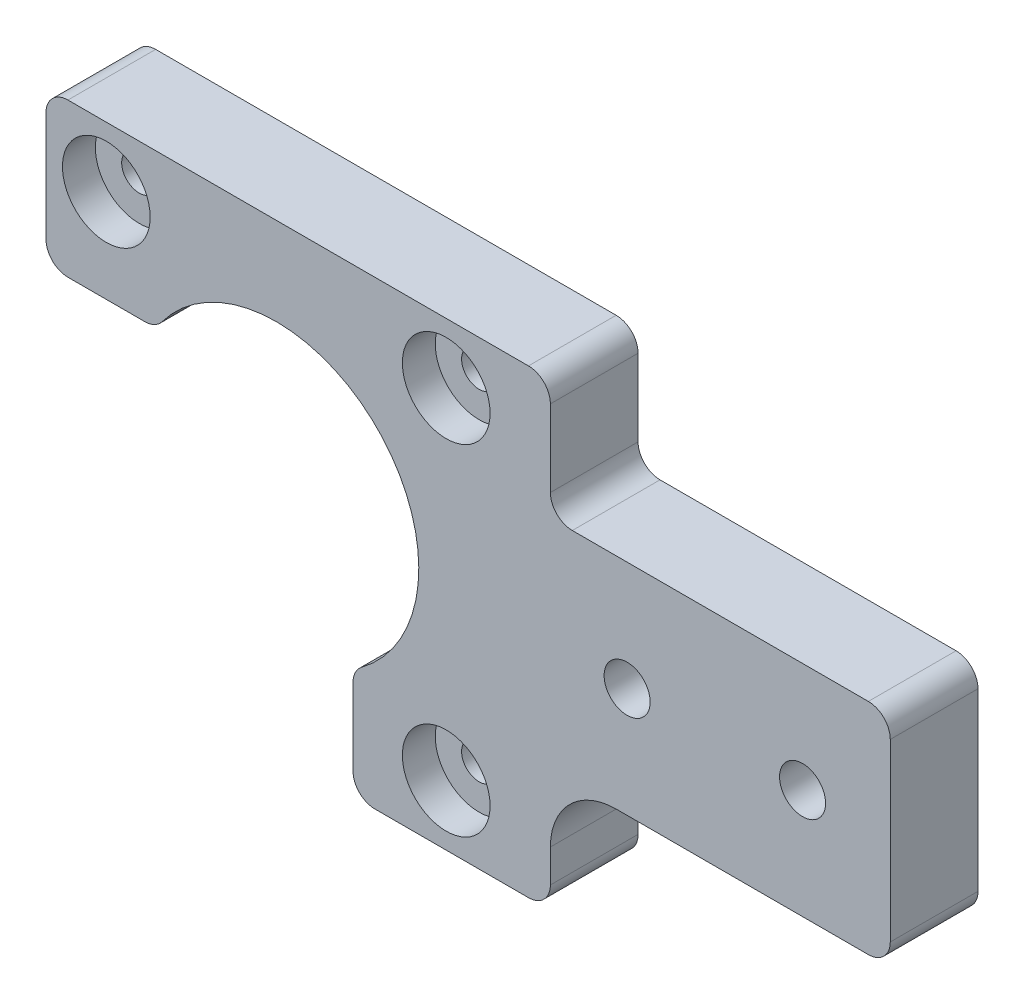
SolidWorks part; units mm, degrees
ref_plane "Plan de face" through (0, 0, 0) normal (0, 0, 1) x (1, 0, 0)
ref_plane "Plan de dessus" through (0, 0, 0) normal (0, 1, 0) x (1, 0, 0)
ref_plane "Plan de droite" through (0, 0, 0) normal (1, 0, 0) x (0, 0, -1)
sketch "Esquisse1" plane through (0, 0, 0) normal (0, 0, 1) x (1, 0, 0)
  line L1 (0, 0) -> (77, 0)
  line L2 (0, 0) -> (0, 42)
  line L3 (0, 42) -> (77, 42)
  line L4 (77, 0) -> (77, 42)
  dimension "D1" = 42
  dimension "D2" = 77
extrude "Boss.-Extru.1" add sketch "Esquisse1" along normal blind 8
sketch "Esquisse3" plane through (0, 0, 8) normal (0, 0, 1) x (1, 0, 0)
  line L0 (42, 42) -> (42, 0) construction
  line L1 (77, 42) -> (0, 42) construction
  line L2 (0, 0) -> (77, 0) construction
  line L3 (0, 42) -> (0, 0) construction
  circle A0 centre (5.5, 36.5) radius 4
  circle A1 centre (36.5, 36.5) radius 4
  circle A2 centre (36.5, 5.5) radius 4
  dimension "D2" = 8
  dimension "D3" = 8
  dimension "D4" = 8
  dimension "D1" = 42
  dimension "D5" = 5.5
  dimension "D6" = 5.5
  dimension "D7" = 5.5
  dimension "D8" = 5.5
  dimension "D9" = 5.5
  dimension "D10" = 5.5
extrude "Enlèv. mat.-Extru.1" cut sketch "Esquisse3" against normal blind 3
sketch "Esquisse4" plane through (0, 0, 8) normal (0, 0, 1) x (1, 0, 0)
  line L0 (0, 42) -> (0, 0) construction
  line L1 (77, 42) -> (0, 42) construction
  circle A0 centre (21, 21) radius 13
  dimension "D1" = 26
  dimension "D2" = 21
  dimension "D3" = 21
extrude "Enlèv. mat.-Extru.2" cut sketch "Esquisse4" against normal through all
sketch "Esquisse5" plane through (0, 0, 8) normal (0, 0, 1) x (1, 0, 0)
  line L1 (0, 0) -> (28, 0)
  line L2 (0, 0) -> (0, 28)
  line L3 (0, 28) -> (28, 28)
  line L4 (28, 0) -> (28, 28)
  dimension "D1" = 28
  dimension "D2" = 28
extrude "Enlèv. mat.-Extru.3" cut sketch "Esquisse5" against normal through all
sketch "Esquisse10" plane through (0, 0, 5) normal (0, 0, 1) x (1, 0, 0)
  circle A0 centre (5.5, 36.5) radius 1.6
  circle A1 centre (36.5, 36.5) radius 1.6
  circle A2 centre (36.5, 5.5) radius 1.6
  dimension "D1" = 3.2
  dimension "D2" = 3.2
  dimension "D3" = 3.2
extrude "Enlèv. mat.-Extru.4" cut sketch "Esquisse10" against normal through all
sketch "Esquisse11" plane through (0, 0, 8) normal (0, 0, 1) x (1, 0, 0)
  line L0 (28, 0) -> (28, 10.0455) construction
  line L1 (77, 0) -> (46, 0)
  line L2 (77, 0) -> (77, 11)
  line L3 (77, 11) -> (46, 11)
  line L4 (46, 0) -> (46, 11)
  line L7 (77, 42) -> (46, 42)
  line L8 (77, 42) -> (77, 31)
  line L9 (77, 31) -> (46, 31)
  line L10 (46, 42) -> (46, 31)
  dimension "D1" = 18
  dimension "D2" = 11
  dimension "D3" = 11
  dimension "D4" = 18
extrude "Enlèv. mat.-Extru.5" cut sketch "Esquisse11" against normal through all
sketch "Esquisse12" plane through (0, 0, 8) normal (0, 0, 1) x (1, 0, 0)
  line L0 (46, 42) -> (0, 42) construction
  line L1 (77, 11) -> (77, 31) construction
  circle A0 centre (53, 21) radius 2.1
  circle A1 centre (69, 21) radius 2.1
  dimension "D1" = 4.2
  dimension "D2" = 4.2
  dimension "D3" = 21
  dimension "D4" = 21
  dimension "D5" = 8
  dimension "D6" = 16
extrude "Enlèv. mat.-Extru.6" cut sketch "Esquisse12" against normal through all
fillet "Congé1" radius 6 1 edges at (46, 11, 4)
fillet "Congé2" radius 2 10 edges at (28, 10.0455, 4) (0, 42, 4) (77, 11, 4) (10.0455, 28, 4) (0, 28, 4) (28, 0, 4) (46, 0, 4) (46, 42, 4) (46, 31, 4) (77, 31, 4)
